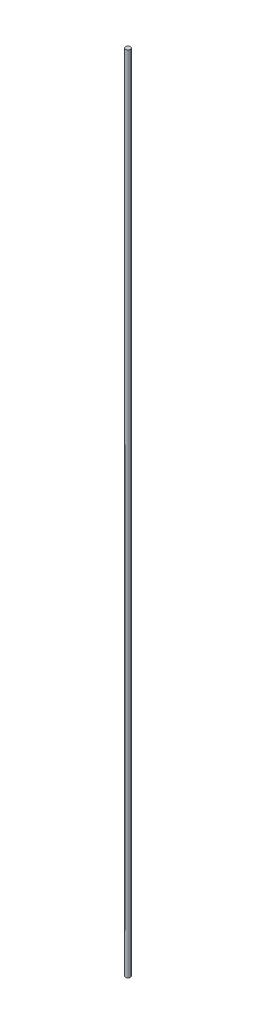
SolidWorks part; units mm, degrees
ref_plane "Спереди" through (0, 0, 0) normal (0, 0, 1) x (1, 0, 0)
ref_plane "Сверху" through (0, 0, 0) normal (0, 1, 0) x (1, 0, 0)
ref_plane "Справа" through (0, 0, 0) normal (1, 0, 0) x (0, 0, -1)
sketch "Эскиз2" plane through (0, 0, 0) normal (0, 0, 1) x (1, 0, 0)
  line L0 (0, 350.0223) -> (-5, 350.0223) construction
  line L5 (-2.5, 350.0223) -> (0, 350.0223)
  line L6 (-2.5, 350.0223) -> (-2.5, -477.3777)
  line L7 (-2.5, -477.3777) -> (0, -477.3777)
  line L8 (0, 350.0223) -> (0, -477.3777)
  line L9 (-2.5, 350.0223) -> (0, -477.3777) construction
  line L10 (-2.5, -477.3777) -> (0, 350.0223) construction
  line L13 (501.5, -477.3777) -> (-28.5, -477.3777) construction
  point P0 (-1.25, -63.6777)
  point P12 (0, 0)
  dimension "D1" = 2.5
revolve "Повернуть1" add sketch "Эскиз2" angle 360 about L6
equation "\"Ширина груза\"= 420"
equation "\"Глубина груза\"= 490"
equation "\"Высота груза\"= 297"
equation "\"Ширина ячейки\"= \"Ширина груза\" + 10"
equation "\"Глубина ячейки\"= \"Глубина груза\" + 10"
equation "\"Высота ячейки\"= \"Высота груза\" + 10 + 13"
equation "\"Колво ячеек ширина\"= 2"
equation "\"Колво ячеек высота\"= 2"
equation "\"Толщина стенки\" = \"Толщина тонких панелей\""
equation "\"Крепление дверцы\"= 5 "
equation "\"Ширина рейки\"= \"Толщина шестерни\""
equation "\"Высота рейки\"= 20"
equation "\"Высота пола\" = 2*\"Толщина тонких панелей\""
equation "\"Колво полозьев\"= 5"
equation "\"Отступ рейки\"= 20"
equation "\"Глубина каретки\"= \"Глубина ячейки\" + 30 + \"Мотор Y высота корпуса\" + 20"
equation "\"Длинна рейки\" = (\"Ширина ячейки\"+\"Толщина вертикальных стенок\"+\"Крепление дверцы\")*\"Колво ячеек ширина\"+\"Ширина ячейки выгрузки\"*\"Колво выгрузки\"+\"Толщина вертикальных стенок\"+2*\"Отступ крепления мотора фиксации\"-\"Крепление дверцы\"*\"Колво ячеек ширина\""
equation "\"Отступ шпильки\"= 26"
equation "\"Диаметр шпильки\"= 5"
equation "\"Длинна шпильки\" = (\"Высота ячейки\"+\"Толщина горизонтальных плит\"+\"Высота пола\")*\"Колво ячеек высота\"+2*(\"Толщина горизонтальных плит\"+\"Отступ рейки\")"
equation "\"D1@Эскиз2\"= \"Диаметр шпильки\" / 2"
equation "\"Ширина пластины\"= 50  "
equation "\"Высота зона выгрузки\"= \"Высота ячейки\" * 2 + \"Толщина стенки\" * 2"
equation "\"Колво выгрузки\"= 1"
equation "\"Отступ крепления мотора фиксации\" = (\"Ширина пластины\"+20-\"Толщина вертикальных стенок\")/2"
equation "\"Мотор X ширина корпуса\"= 42.3"
equation "\"Мотор X высота корпуса\"= 42.3"
equation "\"Мотор X длина корпуса\"= 40"
equation "\"Мотор X вылет вала\"= 19.8"
equation "\"Мотор Y ширина корпуса\"= 42.3"
equation "\"Мотор Y высота корпуса\"= 42.3"
equation "\"Мотор Y длина корпуса\"= 48"
equation "\"Мотор Y вылет вала\"= 30"
equation "\"Мотор Z ширина корпуса\"= 42"
equation "\"Мотор Z высота корпуса\"= 42"
equation "\"Мотор Z длина корпуса\"= 40"
equation "\"Мотор Z вылет вала\"= 23"
equation "\"Мотор диаметр вала ПРЕДВ\"= 5"
equation "\"Мотор шаг крепления ПРЕДВ\"= 31"
equation "\"Мотор диаметр отверстий ПРЕДВ\"= 3"
equation "\"Мотор глубина отверстий ПРЕДВ\"= 4.5"
equation "\"Мотор диаметр буртика ПРЕДВ\"= 22"
equation "\"Мотор высота буртика ПРЕДВ\"= 2"
equation "\"Мотор диаметр шкива ПРЕДВ\"= 16"
equation "\"Мотор длина шкива ПРЕДВ\"= 12"
equation "\"Мотор отступ шкива ПРЕДВ\"= 5"
equation "\"Мотор X шаг градусов\"= 1.8"
equation "\"Мотор X ток А\"= 1.5"
equation "\"Мотор X сопротивление Ом\"= 1.3"
equation "\"Мотор X индуктивность мГн\"= 2"
equation "\"Мотор Y шаг градусов\"= 1.8"
equation "\"Мотор Y ток А\"= 2.2"
equation "\"Мотор Y сопротивление Ом\"= 0.9"
equation "\"Мотор Y индуктивность мГн\"= 2"
equation "\"Мотор Z шаг градусов\"= 1.8"
equation "\"Мотор Z ток А\"= 1"
equation "\"Мотор Z сопротивление Ом\"= 4"
equation "\"Мотор Z индуктивность мГн\"= 8"
equation "\"Мотор Y диаметр ротора\"= 25.78"
equation "\"Ширина ячейки выгрузки\" = \"Ширина ячейки\"+\"Толщина вертикальных стенок\"+2*\"Отступ крепления мотора фиксации\""
equation "\"Толщина тонких панелей\"= 6"
equation "\"Толщина вертикальных стенок\"= 18"
equation "\"Толщина горизонтальных плит\"= 18"
equation "\"Базовая высота корпуса\"= (\"Высота ячейки\"+\"Толщина тонких панелей\"+\"Высота пола\")*\"Колво ячеек высота\"+6*\"Толщина тонких панелей\"+\"Мотор X ширина корпуса\"+\"Мотор Y ширина корпуса\"+75"
equation "\"Высота корпуса\"= (\"Высота ячейки\"+\"Толщина горизонтальных плит\"+\"Высота пола\")*\"Колво ячеек высота\"+2*\"Толщина горизонтальных плит\"+4*\"Толщина тонких панелей\"+\"Мотор X ширина корпуса\"+\"Мотор Y ширина корпуса\"+75"
equation "\"Смещение центра корпуса\"= (\"Высота корпуса\"-\"Базовая высота корпуса\")/2-(\"Толщина горизонтальных плит\"-\"Толщина тонких панелей\")"
equation "\"Отметка пола\"= -\"Базовая высота корпуса\"/2+\"Толщина тонких панелей\""
equation "\"Отметка потолка\"= \"Отметка пола\"+\"Высота корпуса\"-2*\"Толщина горизонтальных плит\""
equation "\"Отметка верхней полки\"= \"Отметка потолка\"-(28+\"Толщина тонких панелей\")-\"Высота ячейки\"-\"Высота пола\""
equation "\"Отметка нижней полки\"= \"Отметка верхней полки\"-\"Высота ячейки\"-\"Высота пола\"-\"Толщина горизонтальных плит\""
